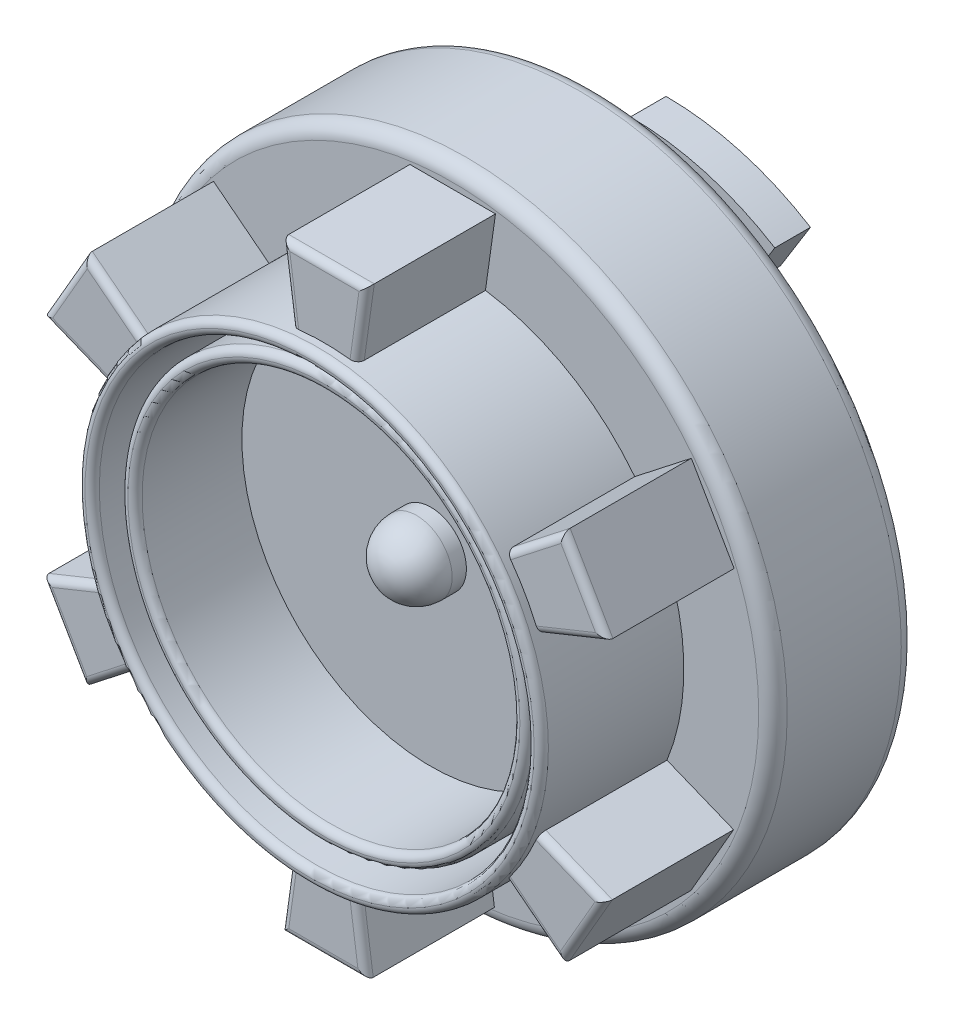
SolidWorks part; units mm, degrees
ref_plane "Front Plane" through (0, 0, 0) normal (0, 0, 1) x (1, 0, 0)
ref_plane "Top Plane" through (0, 0, 0) normal (0, 1, 0) x (1, 0, 0)
ref_plane "Right Plane" through (0, 0, 0) normal (1, 0, 0) x (0, 0, -1)
sketch "Sketch1" plane through (0, 0, 0) normal (0, 0, 1) x (1, 0, 0)
  circle A0 centre (0, 0) radius 41.275
  dimension "D1" = 82.55
extrude "Boss-Extrude1" add sketch "Sketch1" along normal blind 25.4
sketch "Sketch2" plane through (0, 0, 25.4) normal (0, 0, 1) x (1, 0, 0)
  circle A0 centre (0, 0) radius 36.068
  dimension "D1" = 72.136
extrude "Cut-Extrude1" cut sketch "Sketch2" against normal blind 25.4
sketch "Sketch3" plane through (0, 0, 0) normal (0, 0, -1) x (-1, 0, 0)
  circle A0 centre (0, 0) radius 57.15
  dimension "D1" = 114.3
extrude "Boss-Extrude2" add sketch "Sketch3" along normal blind 25.4
sketch "Sketch4" plane through (0, 0, -25.4) normal (0, 0, -1) x (-1, 0, 0)
  circle A0 centre (0, 0) radius 29.21
  dimension "D1" = 58.42
extrude "Cut-Extrude2" cut sketch "Sketch4" against normal through all
sketch "Sketch6" plane through (0, 0, -25.4) normal (0, 0, -1) x (-1, 0, 0)
  line L0 (0, 63.2231) -> (0, -63.2231) construction
  line L1 (-76.4882, 0) -> (76.4882, 0) construction
  line L2 (0, 0) -> (24.4547, -40.1251) construction
  line L3 (18.5063, -30.365) -> (24.4547, -40.1251)
  line L4 (0, 35.56) -> (0, 50.8)
  arc A0 (0, 50.8) -> (25.4, 43.9941) centre (0, 0) cw
  arc A1 (25.4, 43.9941) -> (27.139, 41.3524) centre (22.86, 40.4288) cw
  arc A2 (30.48, 35.7635) -> (24.4547, -40.1251) centre (0, 0) cw
  arc A3 (0, 35.56) -> (18.5063, -30.365) centre (0, 0) cw
  circle A4 centre (0, 0) radius 57.15 construction
  arc A5 (27.139, 41.3524) -> (30.48, 35.7635) centre (37.0703, 43.4962) ccw
  arc A6 (0, -46.99) -> (24.4547, -40.1251) centre (0, 0) ccw construction
  point P5 (0, 0)
  point P9 (0, 0)
  dimension "D1" = 50.8
  dimension "D2" = 22.86
  dimension "D3" = 46.99
  dimension "D4" = 25.4
  dimension "D5" = 30.48
  dimension "D6" = 25.4
  dimension "D7" = 15.24
extrude "Cut-Extrude4" cut sketch "Sketch6" against normal blind 22.86
ref_plane "Plane1" through (0, 0, -22.86) normal (0, 0, -1) x (-1, 0, 0)
sketch "Sketch8" plane through (0, 0, -22.86) normal (0, 0, -1) x (-1, 0, 0)
  line L0 (0, 0) -> (24.4547, -40.1251) construction
  line L1 (26.4375, -43.3785) -> (24.4547, -40.1251)
  arc A0 (26.4375, -43.3785) -> (25.4, 43.9941) centre (0, 0) ccw
  circle A1 centre (0, 0) radius 57.15 construction
  arc A2 (24.4547, -40.1251) -> (30.48, 35.7635) centre (0, 0) ccw
  arc A3 (30.48, 35.7635) -> (27.139, 41.3524) centre (37.0703, 43.4962) cw
  arc A5 (25.4, 43.9941) -> (27.139, 41.3524) centre (22.86, 40.4288) cw
extrude "Cut-Extrude5" cut sketch "Sketch8" against normal blind 20.32
sketch "Sketch9" plane through (0, 0, -25.4) normal (0, 0, -1) x (-1, 0, 0)
  line L0 (0, 65.6273) -> (0, -65.6273) construction
  line L1 (0, 44.45) -> (0, 38.608)
  line L2 (0, 0) -> (-23.4488, 37.7618) construction
  line L3 (-20.367, 32.7988) -> (-23.4488, 37.7618)
  arc A0 (0, 44.45) -> (-23.4488, 37.7618) centre (0, 0) ccw
  circle A2 centre (0, 0) radius 57.15 construction
  arc A3 (0, 38.608) -> (-20.367, 32.7988) centre (0, 0) ccw
  point P6 (0, 0)
  dimension "D1" = 3.048
  dimension "D2" = 6.35
  dimension "D3" = 24.384
extrude "Boss-Extrude3" add sketch "Sketch9" along normal blind 6.35
sketch "Sketch10" plane through (0, 0, -31.75) normal (0, 0, -1) x (-1, 0, 0)
  line L0 (0, 0) -> (-23.4488, 37.7618) construction
  line L1 (-20.367, 32.7988) -> (-25.7267, 41.4301)
  line L2 (0, 0) -> (0, 44.45) construction
  line L3 (0, 48.768) -> (0, 38.608)
  arc A0 (-20.367, 32.7988) -> (0, 38.608) centre (0, 0) cw
  arc A3 (0, 38.608) -> (-20.367, 32.7988) centre (0, 0) ccw construction
  arc A4 (-25.7267, 41.4301) -> (0, 48.768) centre (0, 0) cw
  arc A5 (0, 44.45) -> (-23.4488, 37.7618) centre (0, 0) ccw construction
  dimension "D1" = 10.16
  dimension "D2" = 10.16
extrude "Boss-Extrude4" add sketch "Sketch10" along normal blind 6.35
sketch "Sketch11" plane through (0, 0, -25.4) normal (0, 0, -1) x (-1, 0, 0)
  line L0 (0, 0) -> (0, -62.7191) construction
  line L1 (18.5063, -30.365) -> (24.4547, -40.1251) construction
  line L2 (0, -46.228) -> (0, -38.608)
  line L3 (24.0582, -39.4745) -> (20.0925, -32.9677)
  arc A0 (20.0925, -32.9677) -> (0, -38.608) centre (0, 0) cw
  arc A1 (0, 38.608) -> (-20.367, 32.7988) centre (0, 0) ccw construction
  arc A2 (0, -46.228) -> (24.0582, -39.4745) centre (0, 0) ccw
  dimension "D1" = 38.608
  dimension "D2" = 46.228
extrude "Boss-Extrude5" add sketch "Sketch11" along normal blind 6.35
sketch "Sketch12" plane through (0, 0, -31.75) normal (0, 0, -1) x (-1, 0, 0)
  line L2 (0, -38.608) -> (0, -48.768)
  line L3 (0, 0) -> (24.2564, -39.7998) construction
  line L4 (24.0582, -39.4745) -> (24.4547, -40.1251) construction
  line L5 (20.0925, -32.9677) -> (25.38, -41.6434)
  arc A0 (0, -38.608) -> (20.0925, -32.9677) centre (0, 0) ccw
  arc A1 (0, -38.608) -> (20.0925, -32.9677) centre (0, 0) ccw construction
  arc A2 (0, -48.768) -> (25.38, -41.6434) centre (0, 0) ccw
  arc A3 (0, -46.228) -> (24.0582, -39.4745) centre (0, 0) ccw construction
  dimension "D1" = 10.16
extrude "Boss-Extrude6" add sketch "Sketch12" along normal blind 6.35
sketch "Sketch13" plane through (0, 0, -25.4) normal (0, 0, -1) x (-1, 0, 0)
  line L0 (0, 0) -> (-20.367, 32.7988) construction
  line L1 (0, -35.56) -> (0, -50.8)
  line L2 (-24.7888, 39.9196) -> (-18.7591, 30.2095)
  arc A0 (0, -35.56) -> (-18.7591, 30.2095) centre (0, 0) cw
  arc A1 (18.5063, -30.365) -> (0, 35.56) centre (0, 0) ccw construction
  arc A2 (18.5063, -30.365) -> (0, 35.56) centre (0, 0) ccw construction
  arc A3 (0, -50.8) -> (-25.4, -43.9941) centre (0, 0) cw
  arc A4 (-25.4, -43.9941) -> (-27.915, -39.091) centre (-22.86, -39.5947) cw
  arc A5 (-27.915, -39.091) -> (-30.48, -35.7635) centre (-37.0703, -43.4962) ccw
  circle A6 centre (0, 0) radius 57.15 construction
  arc A7 (-30.48, -35.7635) -> (-24.7888, 39.9196) centre (0, 0) cw
  dimension "D3" = 46.99
  dimension "D1" = 15.24
  dimension "D2" = 25.4
  dimension "D4" = 22.86
  dimension "D5" = 30.48
extrude "Cut-Extrude6" cut sketch "Sketch13" against normal blind 22.86
sketch "Sketch14" plane through (0, 0, -22.86) normal (0, 0, -1) x (-1, 0, 0)
  line L0 (0, 0) -> (-25.7267, 41.4301) construction
  line L1 (-26.7987, 43.1564) -> (-24.7888, 39.9196)
  arc A0 (-25.4, -43.9941) -> (-26.7987, 43.1564) centre (0, 0) cw
  arc A1 (-25.4, -43.9941) -> (0, -50.8) centre (0, 0) ccw construction
  arc A2 (-18.7591, 30.2095) -> (0, -35.56) centre (0, 0) ccw construction
  arc A3 (-24.7888, 39.9196) -> (-30.48, -35.7635) centre (0, 0) ccw
  arc A4 (-24.7888, 39.9196) -> (-30.48, -35.7635) centre (0, 0) ccw construction
  arc A5 (-30.48, -35.7635) -> (-27.915, -39.091) centre (-37.0703, -43.4962) cw
  arc A6 (-27.915, -39.091) -> (-25.4, -43.9941) centre (-22.86, -39.5947) ccw
  arc A7 (-27.915, -39.091) -> (-25.4, -43.9941) centre (-22.86, -39.5947) ccw construction
extrude "Cut-Extrude7" cut sketch "Sketch14" against normal blind 20.32
sketch "Sketch15" plane through (0, 0, -25.4) normal (0, 0, -1) x (-1, 0, 0)
  circle A0 centre (0, 0) radius 30.48
  circle A1 centre (0, 0) radius 34.29
  dimension "D1" = 68.58
  dimension "D2" = 60.96
extrude "Cut-Extrude8" cut sketch "Sketch15" against normal blind 12.7
fillet "Fillet1" radius 2.54 1 edges at (-57.15, 0, -25.4)
sketch "Sketch16" plane through (0, 0, 25.4) normal (0, 0, 1) x (1, 0, 0)
  circle A0 centre (0, 0) radius 41.275
  dimension "D1" = 82.55
extrude "Boss-Extrude7" add sketch "Sketch16" against normal blind 25.4
sketch "Sketch17" plane through (0, 0, 25.4) normal (0, 0, 1) x (1, 0, 0)
  circle A1 centre (0, 0) radius 38.735
  circle A2 centre (0, 0) radius 36.195
  dimension "D1" = 72.39
  dimension "D2" = 77.47
extrude "Cut-Extrude9" cut sketch "Sketch17" against normal blind 25.4
sketch "Sketch18" plane through (0, 0, 25.4) normal (0, 0, 1) x (1, 0, 0)
  circle A1 centre (0, 0) radius 33.655
  circle A2 centre (0, 0) radius 6.35
  dimension "D1" = 12.7
  dimension "D2" = 67.31
extrude "Cut-Extrude10" cut sketch "Sketch18" against normal blind 21.59
sketch "Sketch19" plane through (0, 0, 25.4) normal (0, 0, 1) x (1, 0, 0)
  circle A0 centre (0, 0) radius 6.35
  dimension "D1" = 12.7
extrude "Cut-Extrude11" cut sketch "Sketch19" against normal blind 12.7
sketch "Sketch20" plane through (0, 0, 25.4) normal (0, 0, 1) x (1, 0, 0)
  circle A0 centre (0, 0) radius 33.655
  circle A1 centre (0, 0) radius 36.195
  dimension "D1" = 67.31
  dimension "D2" = 72.39
extrude "Cut-Extrude12" cut sketch "Sketch20" against normal blind 2.54
fillet "Fillet2" radius 6.35 1 edges at (6.35, 0, 12.7)
fillet "Fillet3" radius 1.27 2 edges at (36.195, 0, 22.86) (33.655, 0, 22.86)
fillet "Fillet4" radius 1.27 2 edges at (41.275, 0, 25.4) (38.735, 0, 25.4)
sketch "Sketch21" plane through (0, 0, 0) normal (0, 0, 1) x (1, 0, 0)
  line L0 (-5.7444, 40.8733) -> (-7.5255, 53.5469)
  line L1 (-7.5255, 53.5469) -> (7.7145, 53.5469)
  line L2 (7.7145, 53.5469) -> (5.9296, 40.8469)
  line L3 (0, 0) -> (0, 66.7026) construction
  line L4 (42.6102, 33.2907) -> (50.2302, 20.0925)
  line L5 (50.2302, 20.0925) -> (38.3392, 15.2882)
  line L6 (32.5251, 25.4114) -> (42.6102, 33.2907)
  line L7 (50.1357, -20.2561) -> (42.5157, -33.4544)
  line L8 (42.5157, -33.4544) -> (32.4096, -25.5586)
  line L9 (38.2695, -15.4619) -> (50.1357, -20.2561)
  line L10 (7.5255, -53.5469) -> (-7.7145, -53.5469)
  line L11 (-7.7145, -53.5469) -> (-5.9296, -40.8469)
  line L12 (5.7444, -40.8733) -> (7.5255, -53.5469)
  line L13 (-42.6102, -33.2907) -> (-50.2302, -20.0925)
  line L14 (-50.2302, -20.0925) -> (-38.3392, -15.2882)
  line L15 (-32.5251, -25.4114) -> (-42.6102, -33.2907)
  line L16 (-50.1357, 20.2561) -> (-42.5157, 33.4544)
  line L17 (-42.5157, 33.4544) -> (-32.4096, 25.5586)
  line L18 (-38.2695, 15.4619) -> (-50.1357, 20.2561)
  arc A0 (-5.7444, 40.8733) -> (5.9296, 40.8469) centre (0, 0) cw
  circle A1 centre (0, 0) radius 41.275 construction
  arc A2 (32.5251, 25.4114) -> (38.3392, 15.2882) centre (0, 0) cw
  arc A3 (38.2695, -15.4619) -> (32.4096, -25.5586) centre (0, 0) cw
  arc A4 (5.7444, -40.8733) -> (-5.9296, -40.8469) centre (0, 0) cw
  arc A5 (-32.5251, -25.4114) -> (-38.3392, -15.2882) centre (0, 0) cw
  arc A6 (-38.2695, 15.4619) -> (-32.4096, 25.5586) centre (0, 0) cw
  point P32 (0, 0)
  dimension "D1" = 8
  dimension "D2" = 8
  dimension "D3" = 15.24
  dimension "D4" = 12.7
  dimension "D5" = 7.7145
  dimension "D6" = 6
extrude "Boss-Extrude8" add sketch "Sketch21" along normal blind 22.86
fillet "Fillet5" radius 1.27 18 edges at (-6.6349, 47.2101, 22.86) (44.2847, 17.6904, 22.86) (6.822, 47.1969, 22.86) (0.0945, 53.5469, 22.86) (46.4202, 26.6916, 22.86) (37.5677, 29.3511, 22.86) (46.3257, -26.8552, 22.86) (37.4626, -29.5065, 22.86) (44.2026, -17.859, 22.86) (-6.822, -47.1969, 22.86) (-0.0945, -53.5469, 22.86) (6.6349, -47.2101, 22.86) (-37.5677, -29.3511, 22.86) (-46.4202, -26.6916, 22.86) (-44.2847, -17.6904, 22.86) (-37.4626, 29.5065, 22.86) (-44.2026, 17.859, 22.86) (-46.3257, 26.8552, 22.86)
fillet "Fillet6" radius 2.54 1 edges at (-57.15, 0, 0)
